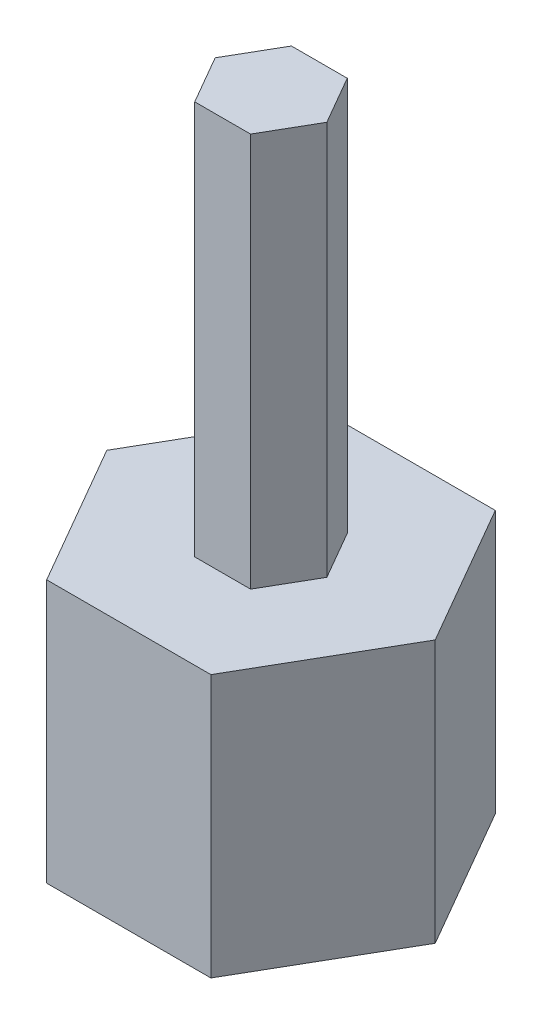
SolidWorks part; units mm, degrees
ref_plane "Front Plane" through (0, 0, 0) normal (0, 0, 1) x (1, 0, 0)
ref_plane "Top Plane" through (0, 0, 0) normal (0, 1, 0) x (1, 0, 0)
ref_plane "Right Plane" through (0, 0, 0) normal (1, 0, 0) x (0, 0, -1)
sketch "Sketch1" plane through (0, 0, 0) normal (0, 1, 0) x (1, 0, 0)
  line L1 (0.85, 0) -> (0.425, 0.7361)
  line L2 (0.425, 0.7361) -> (-0.425, 0.7361)
  line L3 (-0.425, 0.7361) -> (-0.85, 0)
  line L4 (-0.85, 0) -> (-0.425, -0.7361)
  line L5 (-0.425, -0.7361) -> (0.425, -0.7361)
  line L6 (0.425, -0.7361) -> (0.85, 0)
  circle A0 centre (0, 0) radius 0.7361 construction
  point P1 (0, 0)
  dimension "D1" = 0.85
extrude "Boss-Extrude1" add sketch "Sketch1" along normal blind 6
sketch "Sketch2" plane through (0, 0, 0) normal (0, -1, 0) x (1, 0, 0)
  line L1 (2.5, 0) -> (1.25, 2.1651)
  line L2 (1.25, 2.1651) -> (-1.25, 2.1651)
  line L3 (-1.25, 2.1651) -> (-2.5, 0)
  line L4 (-2.5, 0) -> (-1.25, -2.1651)
  line L5 (-1.25, -2.1651) -> (1.25, -2.1651)
  line L6 (1.25, -2.1651) -> (2.5, 0)
  circle A0 centre (0, 0) radius 2.1651 construction
  circle A1 centre (0, 0) radius 2.5 construction
  dimension "D1" = 5
extrude "Boss-Extrude2" add sketch "Sketch2" along normal blind 4
